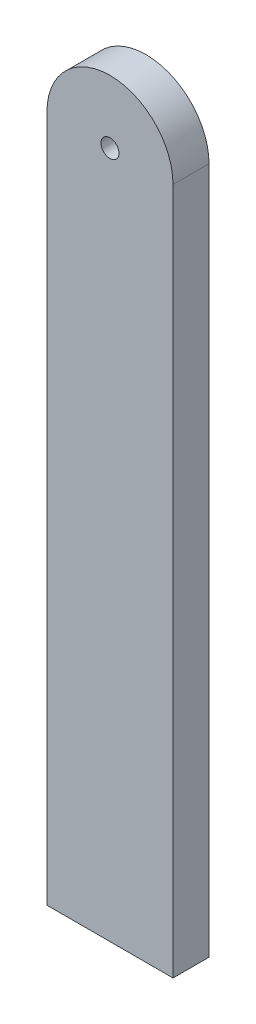
SolidWorks part; units mm, degrees
ref_plane "Front Plane" through (0, 0, 0) normal (0, 0, 1) x (1, 0, 0)
ref_plane "Top Plane" through (0, 0, 0) normal (0, 1, 0) x (1, 0, 0)
ref_plane "Right Plane" through (0, 0, 0) normal (1, 0, 0) x (0, 0, -1)
sketch "Sketch1" plane through (0, 0, 0) normal (0, 0, 1) x (1, 0, 0)
  line L0 (33.3375, -198.4375) -> (-33.3375, -198.4375)
  line L1 (-33.3375, -198.4375) -> (-33.3375, 165.1)
  line L2 (33.3375, 165.1) -> (33.3375, -198.4375)
  line L3 (-33.3375, -16.6687) -> (33.3375, -16.6687) construction
  line L4 (0, -198.4375) -> (0, 198.4375) construction
  arc A0 (-33.3375, 165.1) -> (33.3375, 165.1) centre (0, 165.1) cw
  circle A1 centre (0, 165.1) radius 4.7625
  point P9 (0, 0)
  dimension "D3" = 9.525
  dimension "D1" = 66.675
  dimension "D2" = 396.875
extrude "Boss-Extrude1" add sketch "Sketch1" along normal mid plane 19.05
